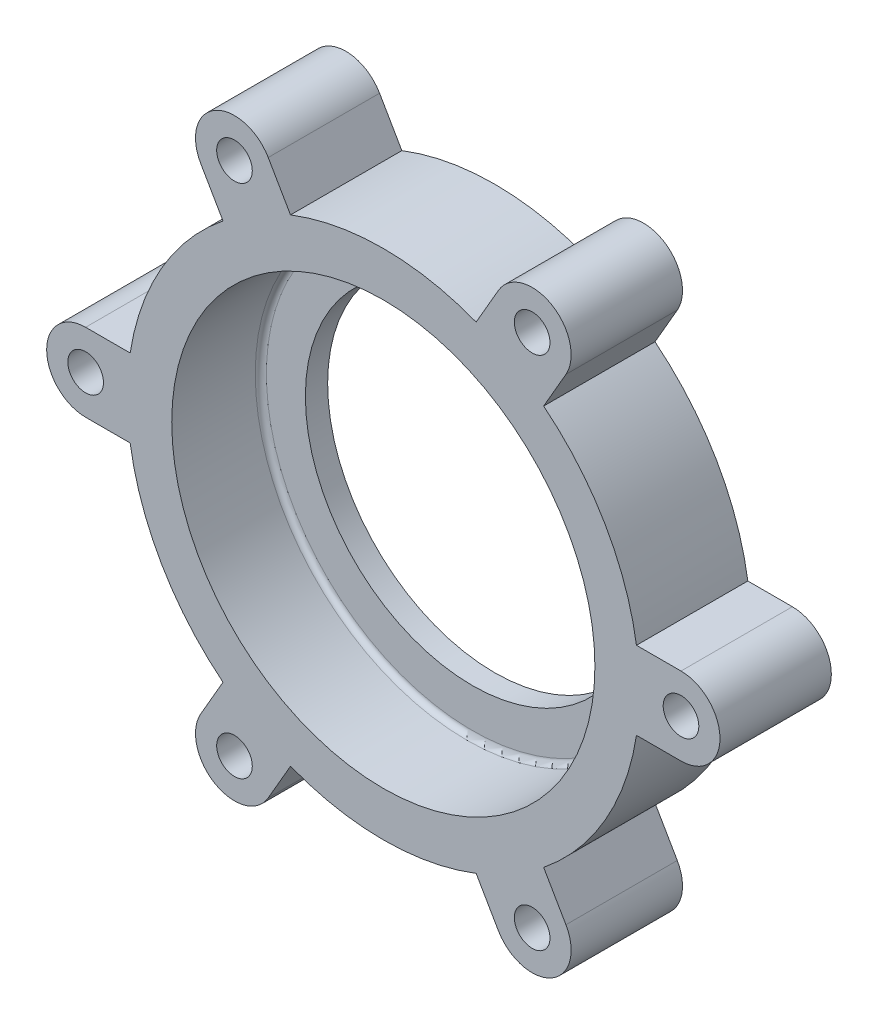
SolidWorks part; units mm, degrees
ref_plane "Front Plane" through (0, 0, 0) normal (0, 0, 1) x (1, 0, 0)
ref_plane "Top Plane" through (0, 0, 0) normal (0, 1, 0) x (1, 0, 0)
ref_plane "Right Plane" through (0, 0, 0) normal (1, 0, 0) x (0, 0, -1)
sketch "Sketch1" plane through (0, 0, 0) normal (0, 0, 1) x (1, 0, 0)
  line L0 (113.6607, 17.5) -> (133.6607, 17.5)
  line L1 (55, 0) -> (-55, 0) construction
  line L2 (113.6607, -17.5) -> (133.6607, -17.5)
  line L3 (71.9858, -89.683) -> (81.9858, -107.0035)
  line L4 (41.6749, -107.183) -> (51.6749, -124.5035)
  line L5 (-41.6749, -107.183) -> (-51.6749, -124.5035)
  line L6 (-71.9858, -89.683) -> (-81.9858, -107.0035)
  line L7 (-113.6607, -17.5) -> (-133.6607, -17.5)
  line L8 (-113.6607, 17.5) -> (-133.6607, 17.5)
  line L9 (-71.9858, 89.683) -> (-81.9858, 107.0035)
  line L10 (-41.6749, 107.183) -> (-51.6749, 124.5035)
  line L11 (41.6749, 107.183) -> (51.6749, 124.5035)
  line L12 (71.9858, 89.683) -> (81.9858, 107.0035)
  circle A0 centre (0, 0) radius 95
  circle A1 centre (0, 0) radius 115
  arc A2 (133.6607, 17.5) -> (133.6607, -17.5) centre (133.6607, 0) cw
  circle A3 centre (133.6607, 0) radius 8
  arc A4 (81.9858, -107.0035) -> (51.6749, -124.5035) centre (66.8303, -115.7535) cw
  circle A5 centre (66.8303, -115.7535) radius 8
  arc A6 (-51.6749, -124.5035) -> (-81.9858, -107.0035) centre (-66.8303, -115.7535) cw
  circle A7 centre (-66.8303, -115.7535) radius 8
  arc A8 (-133.6607, -17.5) -> (-133.6607, 17.5) centre (-133.6607, 0) cw
  circle A9 centre (-133.6607, 0) radius 8
  arc A10 (-81.9858, 107.0035) -> (-51.6749, 124.5035) centre (-66.8303, 115.7535) cw
  circle A11 centre (-66.8303, 115.7535) radius 8
  arc A12 (51.6749, 124.5035) -> (81.9858, 107.0035) centre (66.8303, 115.7535) cw
  circle A13 centre (66.8303, 115.7535) radius 8
  circle A14 centre (0, 0) radius 75
  point P45 (0, 0)
  dimension "D1" = 190
  dimension "D3" = 20
  dimension "D5" = 16
  dimension "D7" = 150
  dimension "D4" = 35
  dimension "D2" = 20
  dimension "D6" = 6
extrude "Boss-Extrude1" add sketch "Sketch1" along normal blind 50 contours A1 A0 | A8 L7 A1 L8 A9 | A10 L9 A1 L10 A11 | A12 L11 A1 L12 A13 | A2 L0 A1 L2 A3 | A4 L3 A1 L4 A5 | A6 L5 A1 L6 A7 region at (123.6607, 16.987, 0) region at (111.4215, 8.5274, 0) region at (57.8049, 100.121, 0) region at (76.4577, -98.6482, 0) region at (-57.8049, 100.121, 0) region at (-47.2029, -115.5384, 0) region at (-115.513, 0, 0)
extrude "Boss-Extrude2" add sketch "Sketch1<3>" along normal blind 10 contours A0 A14 region at (-92.313, 0, 0)
sketch "Sketch1<3>" plane through (0, 0, 0) normal (0, 0, 1) x (1, 0, 0) same geometry as "Sketch1"
fillet "Fillet1" radius 2.5 1 edges at (95, 0, 10)
